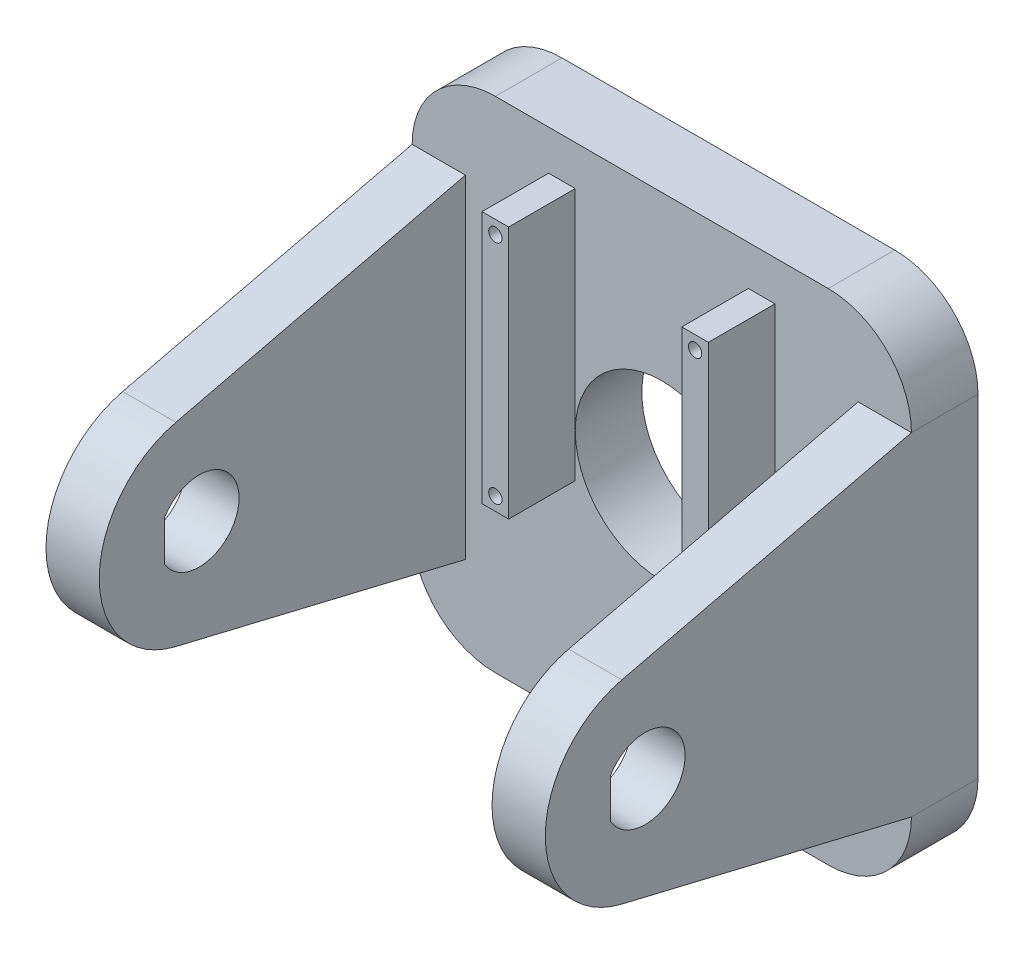
SolidWorks part; units mm, degrees
material "6061 Alloy"
ref_plane "Front Plane" through (0, 0, 0) normal (1, 0, 0) x (0, 1, 0)
ref_plane "Top Plane" through (0, 0, 0) normal (0, 0, 1) x (0, 1, 0)
ref_plane "Right Plane" through (0, 0, 0) normal (0, 1, 0) x (-1, 0, 0)
sketch "Sketch1" plane through (0, 0, 0) normal (0, 0, 1) x (0, 1, 0)
  line L1 (-25, -37.5) -> (25, -37.5)
  line L2 (-37.5, -25) -> (-37.5, 25)
  line L3 (-25, 37.5) -> (25, 37.5)
  line L4 (37.5, -25) -> (37.5, 25)
  line L5 (-37.5, -37.5) -> (37.5, 37.5) construction
  line L6 (-37.5, 37.5) -> (37.5, -37.5) construction
  arc A0 (-25, -37.5) -> (-37.5, -25) centre (-25, -25) cw
  arc A1 (25, -37.5) -> (37.5, -25) centre (25, -25) ccw
  arc A2 (25, 37.5) -> (37.5, 25) centre (25, 25) cw
  arc A3 (-37.5, 25) -> (-25, 37.5) centre (-25, 25) cw
  point P0 (0, 0)
  dimension "D2" = 12.5
  dimension "D1" = 75
extrude "Boss-Extrude1" add sketch "Sketch1" along normal blind 10
sketch "Sketch2" plane through (37.5, 0, 0) normal (1, 0, 0) x (0, 1, 0)
  line L0 (0, 50) -> (0, 0) construction
  line L1 (-25, 10) -> (25, 10) construction
  line L2 (-25, 10) -> (-14.5878, 53.4924)
  line L3 (25, 10) -> (14.5878, 53.4924)
  line L4 (25, 10) -> (25, 0) construction
  line L5 (37.5, 10) -> (25, 10) construction
  line L6 (-3, 55.1962) -> (3, 55.1962)
  circle A0 centre (0, 50) radius 15
  circle A1 centre (0, 50) radius 6
  line M8 (25, 10) -> (-25, 10)
  dimension "D2" = 30
  dimension "D3" = 12
  dimension "D1" = 40
  dimension "D4" = 6
extrude "Boss-Extrude2" add sketch "Sketch2" against normal blind 8 contours L0 A0 L2 M8 | A0 L0 L3 M8 | A1 A0 | L6 A1 region at (37.5, -11.4437, 40.9726) region at (37.5, 11.3969, 24.1864) region at (37.5, -11.3969, 24.1864) region at (37.5, 0, 55.5196)
mirror "Mirror1" about plane through (0, 0, 0) normal (1, 0, 0) of "Boss-Extrude2"
sketch "Sketch3" plane through (0, 0, 10) normal (0, 0, 1) x (1, 0, 0)
  line L0 (0, 37.5) -> (0, -37.5) construction
  line L1 (25, 37.5) -> (-25, 37.5) construction
  line L2 (-25, -37.5) -> (25, -37.5) construction
  circle A0 centre (0, 32.5) radius 1.6
  circle A1 centre (0, -32.5) radius 1.6
  dimension "D1" = 3.2
  dimension "D2" = 5
  dimension "D3" = 5
extrude "Cut-Extrude1" [suppressed] cut sketch "Sketch3" against normal through all
sketch "Sketch4" plane through (0, 0, 10) normal (0, 0, 1) x (1, 0, 0)
  circle A0 centre (0, 0) radius 13
  dimension "D1" = 26
extrude "Cut-Extrude2" cut sketch "Sketch4" against normal through all
sketch "Sketch5" plane through (0, 0, 10) normal (0, 0, 1) x (1, 0, 0)
  line L1 (-17, 31.5) -> (17, 31.5)
  line L2 (-17, 31.5) -> (-17, -6.5)
  line L3 (-17, -6.5) -> (17, -6.5)
  line L4 (17, 31.5) -> (17, -6.5)
  line L5 (-17, 31.5) -> (17, -6.5) construction
  line L6 (-17, -6.5) -> (17, 31.5) construction
  line L7 (-13, -6.5) -> (13, -6.5)
  line L8 (-13, -6.5) -> (-13, 31.5)
  line L9 (-13, 31.5) -> (13, 31.5)
  line L10 (13, -6.5) -> (13, 31.5)
  line L11 (-13, -6.5) -> (13, 31.5) construction
  line L12 (-13, 31.5) -> (13, -6.5) construction
  circle A0 centre (15, -4.5) radius 1
  circle A1 centre (-15, -4.5) radius 1
  circle A2 centre (-15, 29.5) radius 1
  circle A3 centre (15, 29.5) radius 1
  point P12 (0, 12.5)
  point P17 (0, 12.5)
  dimension "D1" = 2
  dimension "D3" = 2
  dimension "D5" = 2
  dimension "D2" = 2
  dimension "D4" = 2
  dimension "D7" = 4
extrude "Boss-Extrude3" add sketch "Sketch5" along normal blind 10 contours L3 L8 L1 L2 A2 A1 | L10 L3 L4 L1 A3 A0 region at (-15, 12.5, 10) region at (15, 12.5, 10)
